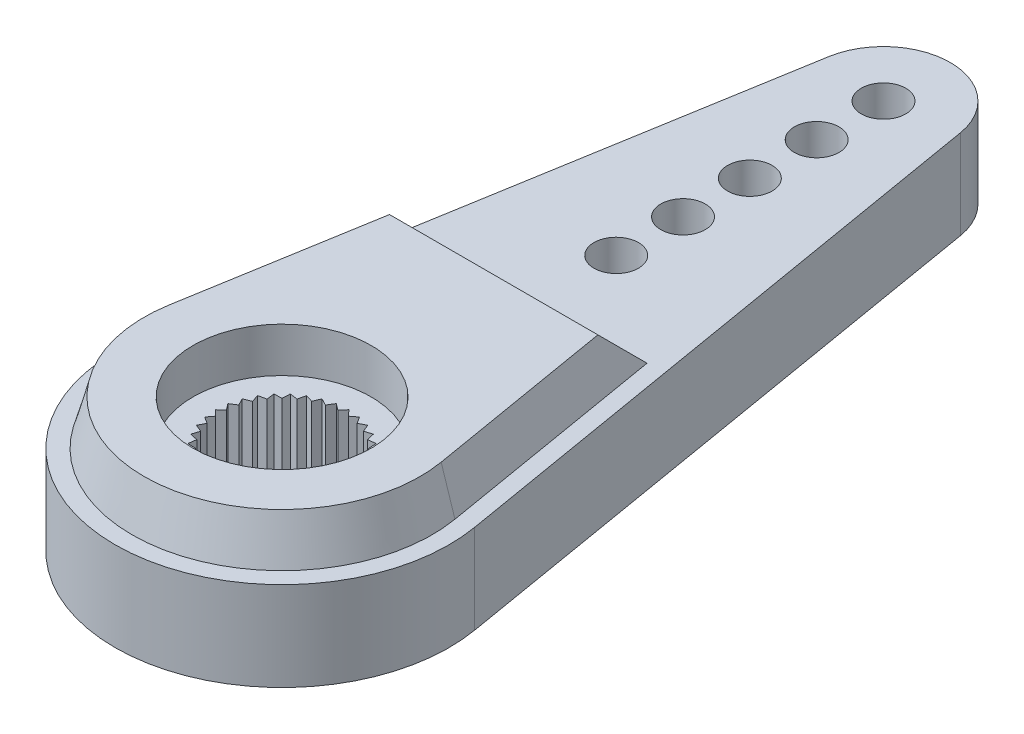
SolidWorks part; units mm, degrees
ref_plane "Alzado" through (0, 0, 0) normal (0, 0, 1) x (1, 0, 0)
ref_plane "Planta" through (0, 0, 0) normal (0, 1, 0) x (1, 0, 0)
ref_plane "Vista lateral" through (0, 0, 0) normal (1, 0, 0) x (0, 0, -1)
sketch "Croquis1" plane through (0, 0, 0) normal (0, 1, 0) x (1, 0, 0)
  line L0 (-2.958, 27.5) -> (-7.3951, 1.25)
  line L1 (2.958, 27.5) -> (7.3951, 1.25)
  line L2 (-6.0851, 9) -> (6.0851, 9)
  line L3 (-6.0851, 8.5) -> (6.1696, 8.5)
  line L4 (-2.465, 27.4167) -> (-6.9021, 1.1667)
  line L5 (2.465, 27.4167) -> (6.9021, 1.1667)
  line L6 (-6.0851, 8.5) -> (6.0851, 8.5) construction
  line L7 (0, 0) -> (-2.7555, 0)
  line L8 (0, 0) -> (-3.7911, 0.3317)
  line L9 (0, 0) -> (-3.1184, 0.5499)
  line L10 (-3, 0) -> (-2.7395, 0.2397)
  line L11 (-2.7395, 0.2397) -> (-2.9544, 0.5209)
  circle A0 centre (0, 0) radius 3
  circle A1 centre (0, 0) radius 4
  circle A2 centre (0, 27) radius 3
  circle A3 centre (0, 0) radius 7.5
  circle A4 centre (0, 15) radius 1
  circle A5 centre (0, 21) radius 1
  circle A6 centre (0, 24) radius 1
  circle A7 centre (0, 27) radius 1
  circle A8 centre (0, 0) radius 7
  circle A9 centre (0, 0) radius 2.75
  circle A10 centre (0, 18) radius 1
  dimension "D2" = 6
  dimension "D4" = 15
  dimension "D5" = 2
  dimension "D9" = 6
  dimension "D16" = 5.5
  dimension "D1" = 15
  dimension "D6" = 3
  dimension "D7" = 3
  dimension "D10" = 9
  dimension "D14" = 10
  dimension "D15" = 5
  dimension "D8" = 3
  dimension "D17" = 3
  dimension "D11" = 0.5
  dimension "D12" = 0.5
  dimension "D13" = 0.5
extrude "Saliente-Extruir1" add sketch "Croquis1" along normal blind 4 contours A6 A2 L0 A3 A4 L1 A5 | A4 A3 A1 | A1 A0 | A6 A2 A7 | A8 A1 | A8 L5 A3 L4 | A3 L5 L3 L4 | A3 L4 L2 L0 | A2 L0 L2 L4 | L5 L2 L4 L3 | A3 L1 L3 L5 | L2 L5 L3 L1 | A2 L5 L2 L1 region at (-4.3679, 0, -17.6791) region at (0, 0, -29.9163) region at (-6.3588, 0, -5.9652) region at (4.3679, 0, -17.6791) region at (-2.1675, 0, -24.6438) region at (-6.8661, 0, -2.5145) region at (0, 0, -8.7494) region at (5.8738, 0, -8.75) region at (0, 0, -7.3481) region at (-5.9226, 0, -6.1379) region at (6.4028, 0, -5.7125) region at (0, 0, -6.802) region at (-3.8869, 0, 0)
extrude "Saliente-Extruir2" add sketch "Croquis1<3>" along normal blind 6 contours A8 L5 A3 L4 | A3 L5 L3 L4 | A8 A1 region at (0, 0, -7.3481) region at (-5.9226, 0, -6.1379) region at (0, 0, -6.802)
sketch "Croquis1<3>" plane through (0, 0, 0) normal (0, 1, 0) x (1, 0, 0) same geometry as "Croquis1"
chamfer "Chaflán1" distance 3 distance2 3 1 edges at (0, 4, -8.5)
chamfer "Chaflán2" distance 3 angle 15 3 edges at (6.1978, 6, -5.3333) (0, 6, 7) (-6.1978, 6, -5.3333) first distance on face at (6.1133, 5, -5.8333) first distance on face at (0, 5, 2.9167) first distance on face at (-6.1133, 5, -5.8333)
extrude "Saliente-Extruir3" add sketch "Croquis1<4>" along normal blind 4 contours L8 A0 L10 | L11 A0 L8 region at (-2.9107, 0, -0.1665) region at (-2.8954, 0, -0.3415)
sketch "Croquis1<4>" plane through (0, 0, 0) normal (0, 1, 0) x (1, 0, 0) same geometry as "Croquis1"
pattern_circular "MatrizC1" count 37 every 10 about axis through (0, 6, 0) along (0, -1, 0) of "Saliente-Extruir3"
equation "\"A\"= 3"
equation "\"D6@Croquis1\"=\"A\""
equation "\"D7@Croquis1\"=\"A\""
equation "\"B\"= 2"
equation "\"D5@Croquis1\"=\"B\""
equation "\"D9@Croquis1\"=\"A\"*2"
equation "\"D8@Croquis1\"=\"A\""
equation "\"D17@Croquis1\"=\"A\""
